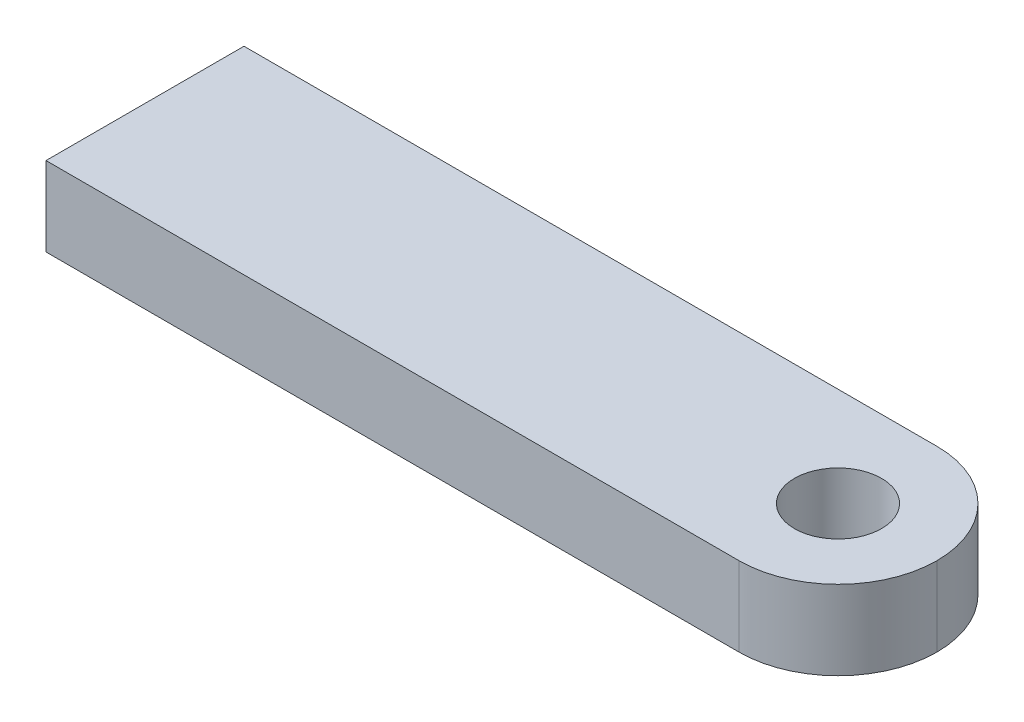
SolidWorks part; units mm, degrees
ref_plane "Front Plane" through (0, 0, 0) normal (0, 0, 1) x (1, 0, 0)
ref_plane "Top Plane" through (0, 0, 0) normal (0, 1, 0) x (1, 0, 0)
ref_plane "Right Plane" through (0, 0, 0) normal (1, 0, 0) x (0, 0, -1)
sketch "Sketch1" plane through (0, 0, 0) normal (0, 1, 0) x (1, 0, 0)
  line L1 (-10, 2.5) -> (10, 2.5)
  line L2 (-10, 2.5) -> (-10, -2.5)
  line L3 (-10, -2.5) -> (10, -2.5)
  line L4 (10, 2.5) -> (10, -2.5)
  dimension "D1" = 20
  dimension "D2" = 5
  dimension "D3" = 10
  dimension "D4" = 2.5
extrude "Boss-Extrude1" add sketch "Sketch1" along normal blind 2
sketch "Sketch2" plane through (0, 2, 0) normal (0, 1, 0) x (1, 0, 0)
  circle A0 centre (7.5, 0) radius 1.1
  dimension "D1" = 2.2
  dimension "D2" = 7.5
extrude "Cut-Extrude1" cut sketch "Sketch2" against normal blind 2
fillet "Fillet1" radius 2.5 2 edges at (10, 1, 2.5) (10, 1, -2.5)
